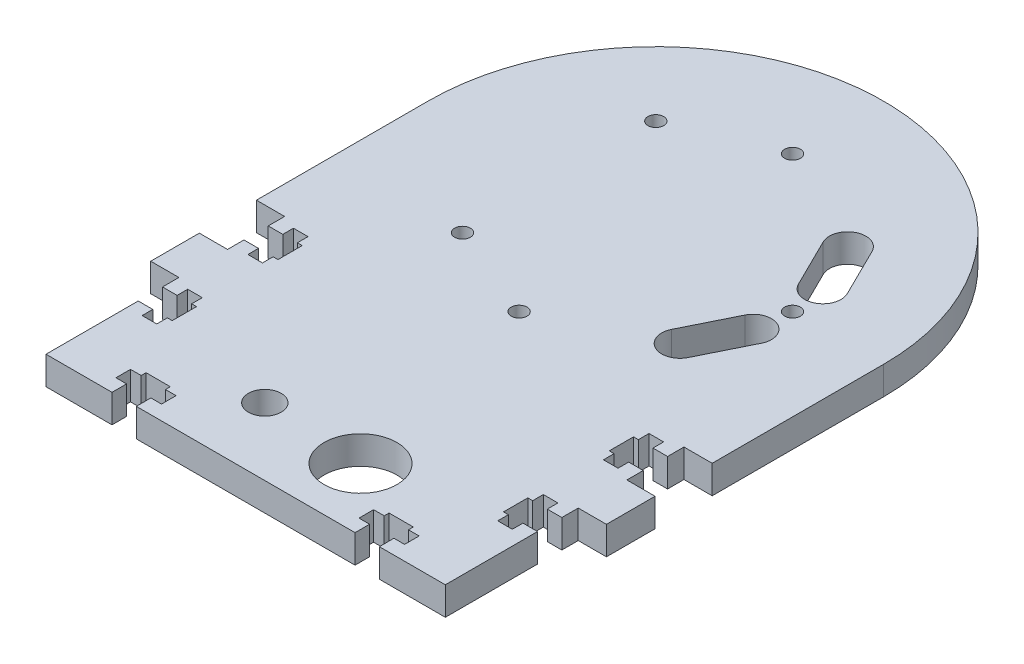
SolidWorks part; units mm, degrees
ref_plane "Front Plane" through (0, 0, 0) normal (0, 0, 1) x (1, 0, 0)
ref_plane "Top Plane" through (0, 0, 0) normal (0, 1, 0) x (1, 0, 0)
ref_plane "Right Plane" through (0, 0, 0) normal (1, 0, 0) x (0, 0, -1)
sketch "Sketch1" plane through (0, 0, 0) normal (0, 1, 0) x (1, 0, 0)
  line L0 (-28.575, 0) -> (0, 0) construction
  line L1 (0, 0) -> (-20.2056, -20.2056) construction
  line L2 (0, 0) -> (-20.2056, 20.2056) construction
  line L3 (27.6326, 7.2781) -> (22.5696, 17.5255) construction
  line L4 (24.2168, 5.5904) -> (19.1538, 15.8379)
  line L5 (31.0484, 8.9657) -> (25.9854, 19.2132)
  line L6 (27.6326, -7.2781) -> (22.5696, -17.5255) construction
  line L7 (24.2168, -5.5904) -> (19.1538, -15.8379)
  line L8 (31.0484, -8.9657) -> (25.9854, -19.2132)
  line L9 (0, -47.625) -> (0, -85.725)
  line L10 (-47.625, 0) -> (-47.625, -85.725)
  line L11 (-47.625, -85.725) -> (47.625, -85.725)
  line L12 (47.625, -85.725) -> (47.625, 0)
  line L13 (-41.7322, -22.947) -> (-41.7322, -85.725) construction
  line L14 (-41.7322, -57.9455) -> (-41.7322, -85.725)
  line L15 (-25.4, -85.725) -> (-25.4, -40.2862) construction
  line L16 (-25.4, -79.629) -> (-25.4, -78.613)
  line L17 (-30.1625, -79.629) -> (-20.6375, -79.629)
  line L18 (-27.94, -85.725) -> (-22.86, -85.725)
  line L19 (-27.94, -85.725) -> (-27.94, -78.613)
  line L20 (-27.94, -78.613) -> (-22.86, -78.613)
  line L21 (-22.86, -85.725) -> (-22.86, -78.613)
  line L22 (-30.1625, -79.629) -> (-30.1625, -82.677)
  line L23 (-30.1625, -82.677) -> (-20.6375, -82.677)
  line L24 (-20.6375, -79.629) -> (-20.6375, -82.677)
  line L25 (-25.4, -82.677) -> (-25.4, -85.725)
  line L26 (-35.6362, -41.8165) -> (-34.6202, -41.8165)
  line L27 (-35.6362, -37.054) -> (-35.6362, -46.579)
  line L28 (-41.7322, -39.2765) -> (-41.7322, -44.3565)
  line L29 (-41.7322, -39.2765) -> (-34.6202, -39.2765)
  line L30 (-34.6202, -39.2765) -> (-34.6202, -44.3565)
  line L31 (-41.7322, -44.3565) -> (-34.6202, -44.3565)
  line L32 (-35.6362, -37.054) -> (-38.6842, -37.054)
  line L33 (-38.6842, -37.054) -> (-38.6842, -46.579)
  line L34 (-35.6362, -46.579) -> (-38.6842, -46.579)
  line L35 (-38.6842, -41.8165) -> (-41.7322, -41.8165)
  line L36 (-35.6362, -63.9145) -> (-34.6202, -63.9145)
  line L37 (-35.6362, -59.152) -> (-35.6362, -68.677)
  line L38 (-41.7322, -61.3745) -> (-41.7322, -66.4545)
  line L39 (-41.7322, -61.3745) -> (-34.6202, -61.3745)
  line L40 (-34.6202, -61.3745) -> (-34.6202, -66.4545)
  line L41 (-41.7322, -66.4545) -> (-34.6202, -66.4545)
  line L42 (-35.6362, -59.152) -> (-38.6842, -59.152)
  line L43 (-38.6842, -59.152) -> (-38.6842, -68.677)
  line L44 (-35.6362, -68.677) -> (-38.6842, -68.677)
  line L45 (-41.7322, -35.8475) -> (-41.7322, -47.7855)
  line L46 (-41.7322, -47.7855) -> (-47.625, -47.7855)
  line L47 (-47.625, -47.7855) -> (-47.625, -57.9455)
  line L48 (-47.625, -57.9455) -> (-41.7322, -57.9455)
  line L49 (-38.6842, -63.9145) -> (-41.7322, -63.9145)
  line L50 (41.7322, -35.8475) -> (47.625, -35.8475)
  line L51 (38.6842, -63.9145) -> (41.7322, -63.9145)
  line L52 (47.625, -57.9455) -> (41.7322, -57.9455)
  line L53 (47.625, -47.7855) -> (47.625, -57.9455)
  line L54 (41.7322, -47.7855) -> (47.625, -47.7855)
  line L55 (41.7322, -35.8475) -> (41.7322, -47.7855)
  line L56 (35.6362, -68.677) -> (38.6842, -68.677)
  line L57 (38.6842, -59.152) -> (38.6842, -68.677)
  line L58 (35.6362, -59.152) -> (38.6842, -59.152)
  line L59 (41.7322, -66.4545) -> (34.6202, -66.4545)
  line L60 (34.6202, -61.3745) -> (34.6202, -66.4545)
  line L61 (41.7322, -61.3745) -> (34.6202, -61.3745)
  line L62 (41.7322, -61.3745) -> (41.7322, -66.4545)
  line L63 (35.6362, -59.152) -> (35.6362, -68.677)
  line L64 (35.6362, -63.9145) -> (34.6202, -63.9145)
  line L65 (38.6842, -41.8165) -> (41.7322, -41.8165)
  line L66 (35.6362, -46.579) -> (38.6842, -46.579)
  line L67 (38.6842, -37.054) -> (38.6842, -46.579)
  line L68 (35.6362, -37.054) -> (38.6842, -37.054)
  line L69 (41.7322, -44.3565) -> (34.6202, -44.3565)
  line L70 (34.6202, -39.2765) -> (34.6202, -44.3565)
  line L71 (41.7322, -39.2765) -> (34.6202, -39.2765)
  line L72 (41.7322, -39.2765) -> (41.7322, -44.3565)
  line L73 (35.6362, -37.054) -> (35.6362, -46.579)
  line L74 (35.6362, -41.8165) -> (34.6202, -41.8165)
  line L75 (25.4, -82.677) -> (25.4, -85.725)
  line L76 (20.6375, -79.629) -> (20.6375, -82.677)
  line L77 (30.1625, -82.677) -> (20.6375, -82.677)
  line L78 (30.1625, -79.629) -> (30.1625, -82.677)
  line L79 (22.86, -85.725) -> (22.86, -78.613)
  line L80 (27.94, -78.613) -> (22.86, -78.613)
  line L81 (27.94, -85.725) -> (27.94, -78.613)
  line L82 (27.94, -85.725) -> (22.86, -85.725)
  line L83 (30.1625, -79.629) -> (20.6375, -79.629)
  line L84 (25.4, -79.629) -> (25.4, -78.613)
  line L85 (41.7322, -57.9455) -> (41.7322, -85.725)
  line L87 (-41.7322, -35.8475) -> (-47.625, -35.8475)
  circle A0 centre (0, 0) radius 28.575 construction
  circle A1 centre (0, 0) radius 47.625
  circle A2 centre (0, 28.575) radius 1.651
  circle A3 centre (0, -28.575) radius 1.651
  circle A4 centre (28.575, 0) radius 1.651
  circle A5 centre (-20.2056, 20.2056) radius 1.651
  circle A6 centre (-20.2056, -20.2056) radius 1.651
  arc A7 (24.2168, 5.5904) -> (31.0484, 8.9657) centre (27.6326, 7.2781) ccw
  arc A8 (25.9854, 19.2132) -> (19.1538, 15.8379) centre (22.5696, 17.5255) ccw
  arc A9 (24.2168, -5.5904) -> (31.0484, -8.9657) centre (27.6326, -7.2781) cw
  arc A10 (25.9854, -19.2132) -> (19.1538, -15.8379) centre (22.5696, -17.5255) cw
  circle A11 centre (10.922, -72.644) radius 7.62
  circle A12 centre (-10.0748, -71.6475) radius 3.429
  point P17 (25.1011, 12.4018)
  point P24 (25.1011, -12.4018)
  dimension "D1" = 3.302
  dimension "D2" = 57.15
  dimension "D3" = 95.25
  dimension "D6" = 3.81
  dimension "D30" = 15.24
  dimension "D29" = 6.858
  dimension "D4" = 45
  dimension "D5" = 45
  dimension "D7" = 11.43
  dimension "D8" = 38.1
  dimension "D9" = 5.8928
  dimension "D10" = 11.938
  dimension "D11" = 25.4
  dimension "D12" = 5.08
  dimension "D13" = 7.112
  dimension "D14" = 9.525
  dimension "D15" = 3.048
  dimension "D16" = 3.048
  dimension "D17" = 5.08
  dimension "D18" = 7.112
  dimension "D19" = 9.525
  dimension "D20" = 3.048
  dimension "D21" = 3.048
  dimension "D22" = 5.08
  dimension "D23" = 7.112
  dimension "D24" = 9.525
  dimension "D25" = 10.16
  dimension "D26" = 3.048
  dimension "D27" = 3.048
  dimension "D28" = 5.969
  dimension "D31" = 35.8475
extrude "Boss-Extrude1" add sketch "Sketch1" along normal blind 5.8928 contours A1 A2 A3 A4 A5 A6 A8 L5 A7 L4 L8 A10 L7 A9 | A1 L10 L87 L45 L29 L33 L32 L27 L30 L31 L34 L46 L48 L14 L39 L43 L42 L37 L40 L41 L44 L11 L19 L23 L22 L17 L20 L21 L24 L9 A12 | A1 L9 L11 L79 L77 L76 L83 L80 L81 L78 L85 L59 L57 L56 L63 L60 L61 L58 L52 L12 L54 L55 L69 L67 L66 L73 L70 L71 L68 L50 A11 region at (25.1963, 0, 58.5983) region at (-24.1092, 0, 59.704) region at (-0.9623, 0, 0)
